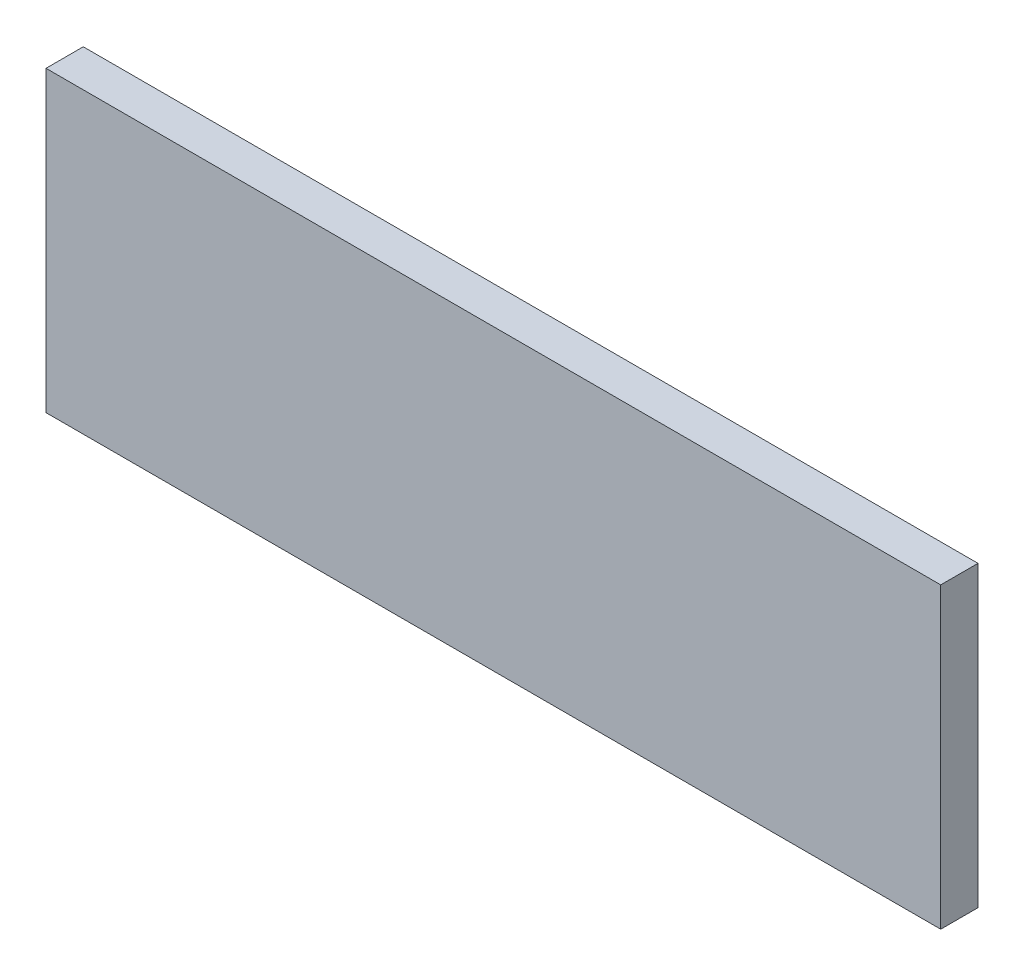
SolidWorks part; units mm, degrees
ref_plane "Front Plane" through (0, 0, 0) normal (0, 0, 1) x (1, 0, 0)
ref_plane "Top Plane" through (0, 0, 0) normal (0, 1, 0) x (1, 0, 0)
ref_plane "Right Plane" through (0, 0, 0) normal (1, 0, 0) x (0, 0, -1)
sketch "Sketch1" plane through (0, 0, 0) normal (0, 0, 1) x (1, 0, 0)
  line L1 (0, 0) -> (304.8, 0)
  line L2 (0, 0) -> (0, -101.6)
  line L3 (0, -101.6) -> (304.8, -101.6)
  line L4 (304.8, 0) -> (304.8, -101.6)
  dimension "D1" = 304.8
  dimension "D2" = 101.6
extrude "Boss-Extrude1" add sketch "Sketch1" along normal blind 12.7
